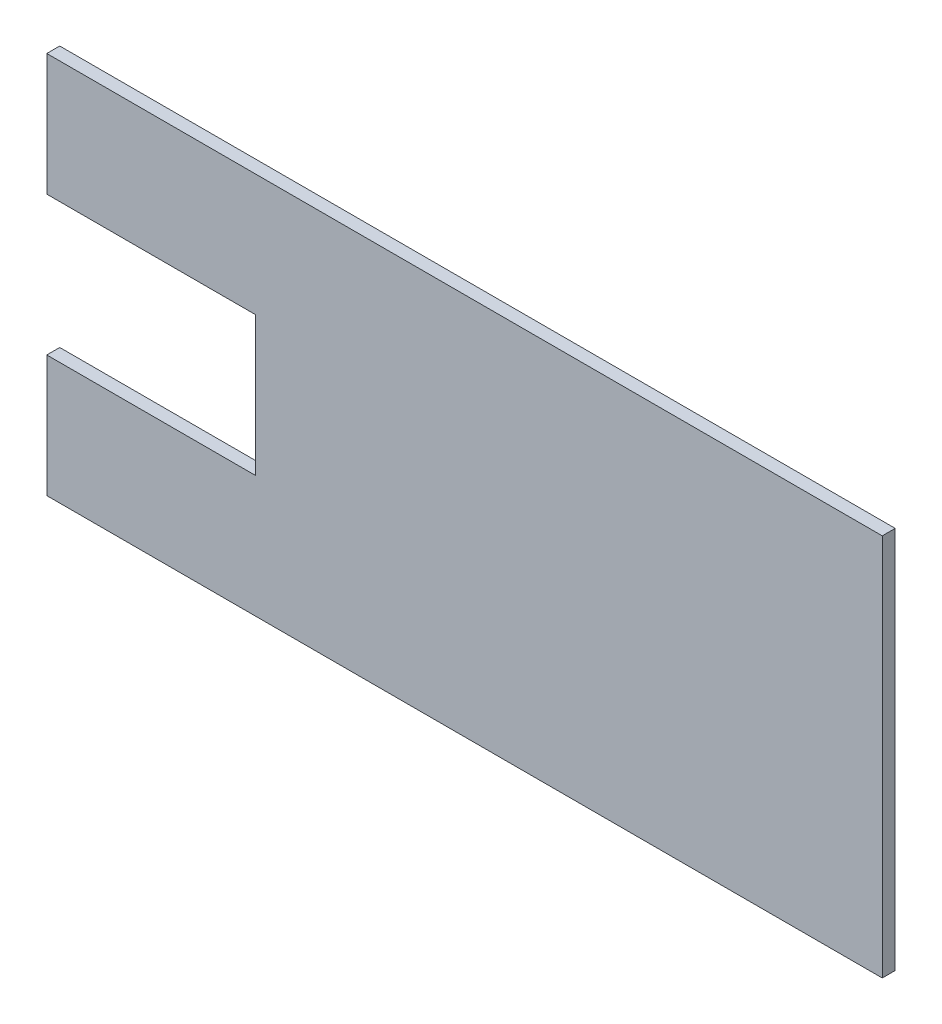
SolidWorks part; units mm, degrees
ref_plane "Front Plane" through (0, 0, 0) normal (0, 0, 1) x (1, 0, 0)
ref_plane "Top Plane" through (0, 0, 0) normal (0, 1, 0) x (1, 0, 0)
ref_plane "Right Plane" through (0, 0, 0) normal (1, 0, 0) x (0, 0, -1)
sketch "Sketch1" plane through (0, 0, 0) normal (0, 0, 1) x (1, 0, 0)
  line L1 (0, 0) -> (152.4, 0)
  line L2 (0, 0) -> (0, 69.85)
  line L3 (0, 69.85) -> (152.4, 69.85)
  line L4 (152.4, 0) -> (152.4, 69.85)
  dimension "D1" = 69.85
  dimension "D2" = 152.4
extrude "Boss-Extrude1" add sketch "Sketch1" along normal blind 2.3622
sketch "Sketch2" plane through (0, 0, 2.3622) normal (0, 0, 1) x (1, 0, 0)
  line L0 (0, 69.85) -> (0, 0) construction
  line L1 (0, 47.625) -> (38.1, 47.625)
  line L2 (0, 47.625) -> (0, 22.225)
  line L3 (0, 22.225) -> (38.1, 22.225)
  line L4 (38.1, 47.625) -> (38.1, 22.225)
  line L5 (152.4, 0) -> (152.4, 69.85) construction
  point P6 (38.1, 34.925)
  point P7 (152.4, 34.925)
  dimension "D1" = 25.4
  dimension "D2" = 38.1
extrude "Cut-Extrude1" cut sketch "Sketch2" against normal through all
